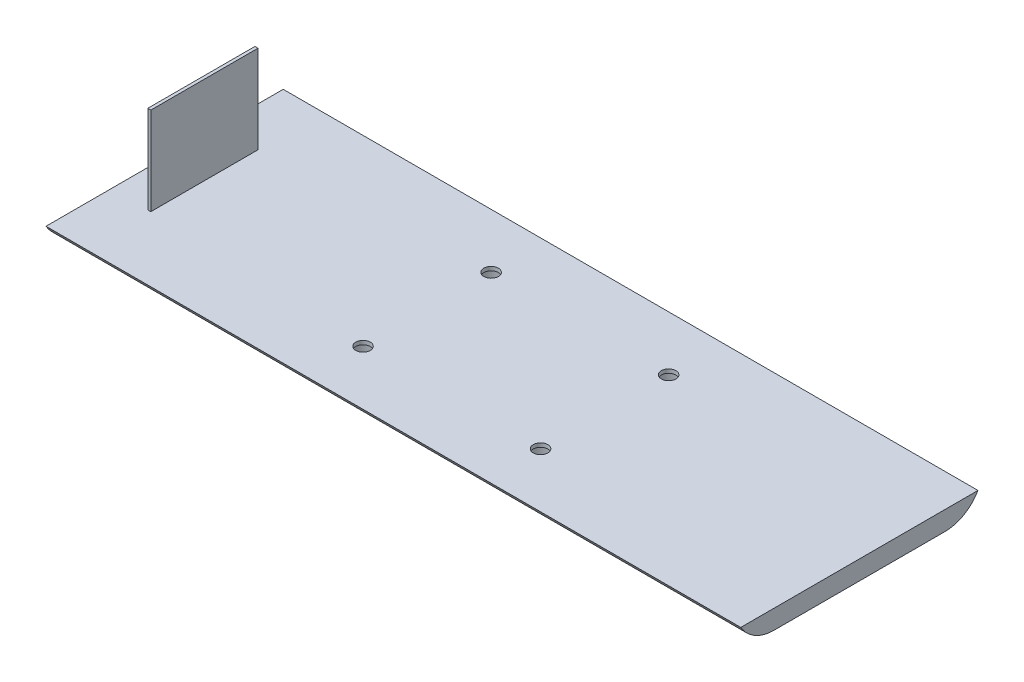
SolidWorks part; units mm, degrees
ref_plane "Front Plane" through (0, 0, 0) normal (0, 0, 1) x (1, 0, 0)
ref_plane "Top Plane" through (0, 0, 0) normal (0, 1, 0) x (1, 0, 0)
ref_plane "Right Plane" through (0, 0, 0) normal (1, 0, 0) x (0, 0, -1)
sketch "Sketch1" plane through (0, 0, 0) normal (0, 1, 0) x (1, 0, 0)
  line L0 (-45.4, 0) -> (45.4, 0) construction
  line L1 (-45.4, 15.5) -> (45.4, 15.5)
  line L2 (-45.4, 15.5) -> (-45.4, -15.5)
  line L3 (-45.4, -15.5) -> (45.4, -15.5)
  line L4 (45.4, 15.5) -> (45.4, -15.5)
  line L5 (0, 15.5) -> (0, -15.5) construction
  point P8 (0, 0)
  dimension "D1" = 31
  dimension "D2" = 90.8
extrude "Boss-Extrude1" add sketch "Sketch1" along normal blind 2.5
sketch "Sketch2" plane through (0, 2.5, 0) normal (0, 1, 0) x (1, 0, 0)
  line L0 (-45.4, 15.5) -> (-45.4, -15.5) construction
  line L1 (-40.6, 7) -> (-40.2, 7)
  line L2 (-40.6, 7) -> (-40.6, -7)
  line L3 (-40.6, -7) -> (-40.2, -7)
  line L4 (-40.2, 7) -> (-40.2, -7)
  line L5 (45.4, 15.5) -> (-45.4, 15.5) construction
  line L6 (-45.4, -15.5) -> (45.4, -15.5) construction
  dimension "D1" = 4.8
  dimension "D2" = 8.5
  dimension "D3" = 8.5
  dimension "D4" = 0.4
extrude "Boss-Extrude2" add sketch "Sketch2" along normal blind 11.5
sketch "Sketch3" plane through (0, 2.5, 0) normal (0, 1, 0) x (1, 0, 0)
  line L0 (-11.1, 8.37) -> (-11.1, 15.5) construction
  line L1 (45.4, 15.5) -> (-45.4, 15.5) construction
  line L2 (12.1, 8.37) -> (12.1, 15.5) construction
  line L3 (-11.1, -8.37) -> (-11.1, -15.5) construction
  line L4 (-45.4, -15.5) -> (45.4, -15.5) construction
  line L5 (12.1, -8.37) -> (12.1, -15.5) construction
  line L6 (-11.1, 8.37) -> (-45.4, 8.37) construction
  line L8 (-45.4, 15.5) -> (-45.4, -15.5) construction
  line L9 (-11.1, -8.37) -> (-45.4, -8.37) construction
  line L10 (-11.1, 8.37) -> (12.1, 8.37) construction
  line L11 (-11.1, -8.37) -> (12.1, -8.37) construction
  circle A0 centre (-11.1, 8.37) radius 0.95
  circle A1 centre (12.1, 8.37) radius 0.95
  circle A2 centre (-11.1, -8.37) radius 0.95
  circle A3 centre (12.1, -8.37) radius 0.95
  dimension "D1" = 7.13
  dimension "D2" = 1.9
  dimension "D3" = 34.3
  dimension "D4" = 23.2
extrude "Cut-Extrude1" cut sketch "Sketch3" against normal blind 14
sketch "Sketch4" plane through (0, 0, 0) normal (0, -1, 0) x (1, 0, 0)
  circle A0 centre (-11.1, 8.37) radius 1.9
  circle A1 centre (-11.1, -8.37) radius 1.9
  circle A2 centre (12.1, 8.37) radius 1.9
  circle A3 centre (12.1, -8.37) radius 1.9
  dimension "D1" = 3.8
extrude "Cut-Extrude2" cut sketch "Sketch4" against normal blind 2
fillet "Fillet1" radius 5 2 edges at (0, 0, -15.5) (0, 0, 15.5)
equation "\"11.5.00mm\"=1"
